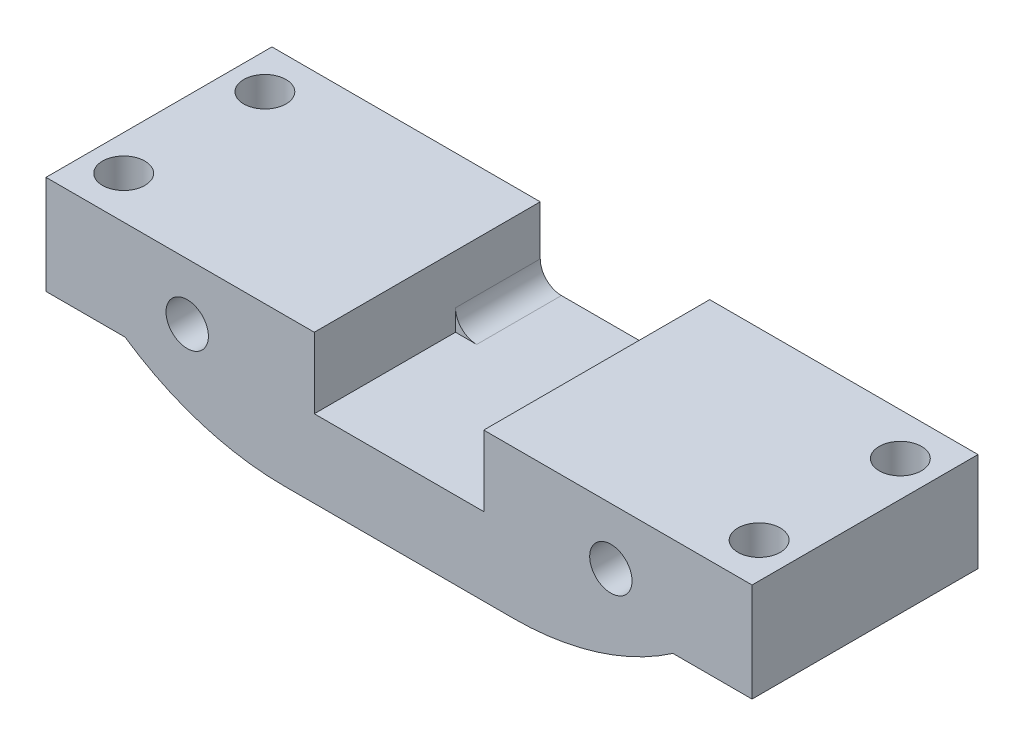
SolidWorks part; units mm, degrees
ref_plane "Front Plane" through (0, 0, 0) normal (0, 0, 1) x (1, 0, 0)
ref_plane "Top Plane" through (0, 0, 0) normal (0, 1, 0) x (1, 0, 0)
ref_plane "Right Plane" through (0, 0, 0) normal (1, 0, 0) x (0, 0, -1)
sketch "Sketch7" plane through (0, 0, 0) normal (0, 0, 1) x (1, 0, 0)
  line L20 (-2, 14.9) -> (11, 14.9)
  line L21 (35, 14.9) -> (48, 14.9)
  line L22 (11, 14.9) -> (17, 14.9)
  line L24 (3.5981, 7.9) -> (-2, 7.9)
  line L25 (3.5981, 7.9) -> (3.5981, 4.4)
  line L26 (42.4, 7.9) -> (42.4, 4.4)
  line L29 (48, 7.9) -> (42.4, 7.9)
  line L31 (48, 14.9) -> (48, 7.9)
  line L32 (-2, 14.9) -> (-2, 7.9)
  line L33 (3.5981, 4.4) -> (42.4, 4.4)
  line L35 (17, 14.9) -> (17, 9.9)
  line L36 (29, 14.9) -> (29, 9.9)
  line L37 (17, 9.9) -> (29, 9.9)
  line L38 (29, 14.9) -> (35, 14.9)
  circle A1 centre (8, 10.9) radius 1.5
  circle A2 centre (38, 10.9) radius 1.5
  dimension "D3" = 5.5981
  dimension "D4" = 13
  dimension "D10" = 12
  dimension "D11" = 3
  dimension "D12" = 5.6
  dimension "D13" = 19
  dimension "D15" = 3
  dimension "D7" = 13
  dimension "D8" = 4
  dimension "D2" = 5
  dimension "D16" = 10
  dimension "D5" = 13
  dimension "D6" = 10
  dimension "D9" = 4
  dimension "D14" = 7
extrude "Boss-Extrude11" add sketch "Sketch7" along normal blind 10 contours L20 L32 L24 L25 L26 L29 L31 L21 A2 A1 region at (22.9997, 9.5395, 0)
ref_plane "Plane2" through (0, 7.9, 0) normal (0, -1, 0) x (-1, 0, 0)
sketch "Sketch8" plane through (0, 7.9, 0) normal (0, -1, 0) x (1, 0, 0)
  line L8 (-2, 0) -> (17, 0) construction
  line L9 (-2, 10) -> (-2, 0) construction
  line L11 (-2, 10) -> (17, 10) construction
  line L12 (48, 10) -> (48, 0) construction
  line L13 (29, 0) -> (48, 0) construction
  line L14 (29, 10) -> (48, 10) construction
  circle A0 centre (0.5, 7) radius 1.5
  circle A1 centre (45.5, 7) radius 1.5
  circle A2 centre (45.5, 3) radius 1.5
  circle A3 centre (0.5, 3) radius 1.5
  dimension "D1" = 3
  dimension "D2" = 3
  dimension "D3" = 2.5
  dimension "D4" = 2.5
  dimension "D5" = 3
  dimension "D6" = 2.5
  dimension "D7" = 3
  dimension "D8" = 3
  dimension "D9" = 2.5
fillet "Fillet1" radius 20 2 edges at (42.4, 4.4, 5) (3.5981, 4.4, 5)
sketch "Sketch9" plane through (0, 0, 0) normal (0, 0, -1) x (-1, 0, 0)
  line L10 (-48, 7.9) -> (-42.4, 7.9)
  line L11 (-31.0973, 4.4) -> (-14.9007, 4.4)
  line L12 (-3.5981, 7.9) -> (2, 7.9)
  line L13 (2, 7.9) -> (2, 14.9)
  line L14 (2, 14.9) -> (-17, 14.9)
  line L15 (-17, 14.9) -> (-17, 9.9)
  line L16 (-17, 9.9) -> (-29, 9.9)
  line L17 (-29, 9.9) -> (-29, 14.9)
  line L18 (-29, 14.9) -> (-48, 14.9)
  line L19 (-48, 14.9) -> (-48, 7.9)
  line L20 (-48, 7.9) -> (-42.4, 7.9)
  line L21 (-31.0973, 4.4) -> (-14.9007, 4.4)
  line L22 (-3.5981, 7.9) -> (2, 7.9)
  line L23 (2, 7.9) -> (2, 14.9)
  line L24 (2, 14.9) -> (-17, 14.9)
  line L25 (-17, 14.9) -> (-17, 11.4)
  line L26 (-18.5, 9.9) -> (-27.5, 9.9)
  line L27 (-29, 11.4) -> (-29, 14.9)
  line L28 (-29, 14.9) -> (-48, 14.9)
  line L29 (-48, 14.9) -> (-48, 7.9)
  arc A0 (-18.5, 9.9) -> (-17, 11.4) centre (-18.5, 11.4) ccw
  arc A1 (-29, 11.4) -> (-27.5, 9.9) centre (-27.5, 11.4) ccw
  arc A2 (-42.4, 7.9) -> (-31.0973, 4.4) centre (-31.0973, 24.4) ccw
  arc A3 (-14.9007, 4.4) -> (-3.5981, 7.9) centre (-14.9007, 24.4) ccw
  arc A4 (-42.4, 7.9) -> (-31.0973, 4.4) centre (-31.0973, 24.4) ccw
  arc A5 (-14.9007, 4.4) -> (-3.5981, 7.9) centre (-14.9007, 24.4) ccw
  circle A6 centre (-38, 10.9) radius 1.5 construction
  circle A7 centre (-8, 10.9) radius 1.5 construction
  circle A8 centre (-38, 10.9) radius 1.5
  circle A9 centre (-8, 10.9) radius 1.5
  dimension "D2" = 3
  dimension "D1" = 0
extrude "Boss-Extrude12" add sketch "Sketch9" along normal blind 6
sketch "Sketch10" plane through (0, 14.9, 0) normal (0, 1, 0) x (1, 0, 0)
  line L0 (29, 6) -> (48, 6) construction
  line L2 (-2, -10) -> (-2, 6) construction
  line L3 (48, -10) -> (48, 6) construction
  line L4 (-2, 6) -> (17, 6) construction
  line L5 (-2, -10) -> (17, -10) construction
  line L6 (29, -10) -> (48, -10) construction
  circle A0 centre (0.5, -7) radius 1.5 construction
  circle A1 centre (0.5, -7) radius 1.5
  circle A2 centre (0.5, 3) radius 1.5
  circle A3 centre (45.5, -7) radius 1.5 construction
  circle A4 centre (45.5, -7) radius 1.5
  circle A5 centre (45.5, 3) radius 1.5
  dimension "D2" = 2.5
  dimension "D1" = 3
  dimension "D3" = 2.5
  dimension "D4" = 2.5
  dimension "D5" = 2.5
  dimension "D6" = 3
  dimension "D7" = 3
  dimension "D8" = 3
extrude "Cut-Extrude1" cut sketch "Sketch10" against normal through all both and the other way through all
